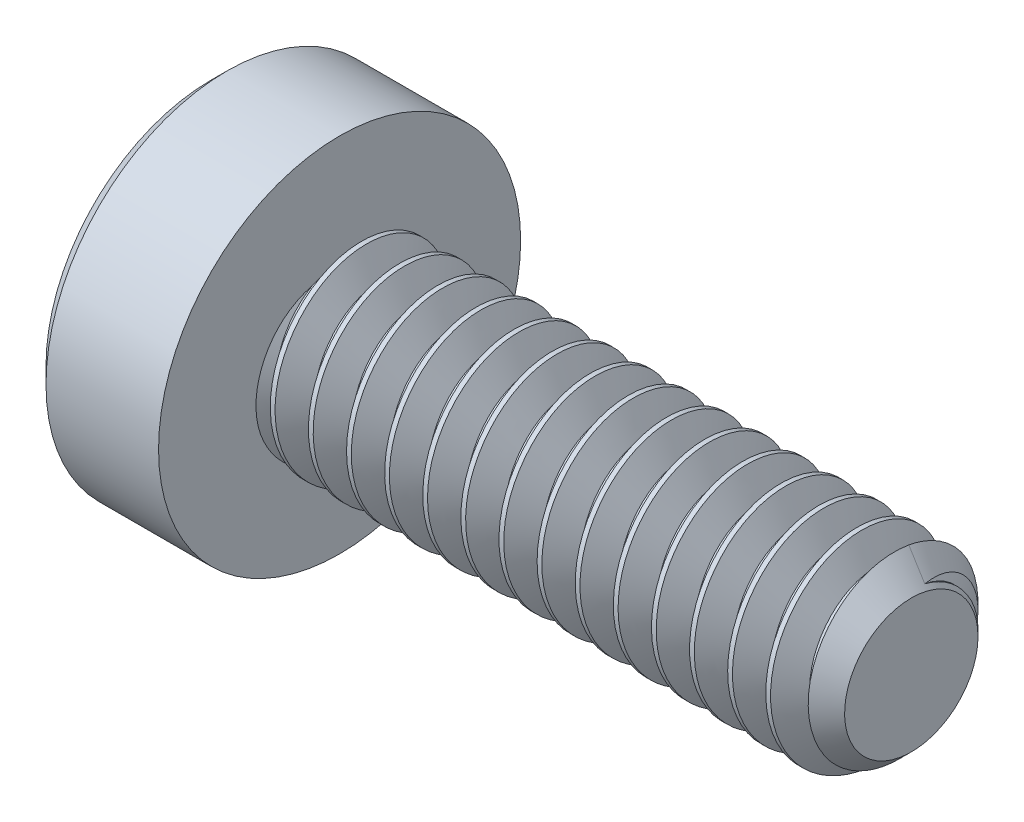
SolidWorks part; units mm, degrees
ref_plane "Front Plane" through (0, 0, 0) normal (0, 0, 1) x (1, 0, 0)
ref_plane "Top Plane" through (0, 0, 0) normal (0, 1, 0) x (1, 0, 0)
ref_plane "Right Plane" through (0, 0, 0) normal (1, 0, 0) x (0, 0, -1)
sketch "Sketch1" plane through (0, 0, 0) normal (0, 0, 1) x (1, 0, 0)
  line L0 (3, 0) -> (-3, 0) construction
  line L1 (3, 1) -> (3, -1) construction
  line L2 (-3, 1.9) -> (-3, -1.9) construction
  line L3 (-3, 1.9) -> (-4.1813, 1.9) construction
  line L4 (-4.1813, 1.9) -> (-4.35, 1.7312) construction
  line L5 (-4.35, 1.7312) -> (-4.35, -1.7313) construction
  line L6 (-4.35, -1.7313) -> (-4.1813, -1.9) construction
  line L7 (-4.1813, -1.9) -> (-3, -1.9) construction
  point P7 (-3.375, 0)
  point P12 (1.4, -1)
  dimension "D1" = 45
  dimension "Dec." = 2
  dimension "Length" = 6
  dimension "Head Dia" = 3.8
  dimension "Head Height" = 1.35
  dimension "Hex Depth" = 0.975
  dimension "Chamfer" = 0.1688
  dimension "D2" = 1.6
ref_plane "Plane1" through (3, 0, 0) normal (1, 0, 0) x (0, 0, -1)
ref_plane "Plane2" through (-4.35, 0, 0) normal (1, 0, 0) x (0, 0, -1)
sketch "Sketch2" plane through (3, 0, 0) normal (1, 0, 0) x (0, 0, -1)
  circle A0 centre (0, 0) radius 1
extrude "Boss-Extrude1" add sketch "Sketch2" against normal up to vertex (6 mm away) up to point (-3, 0, 0)
sketch "Sketch3" plane through (3, 0, 0) normal (1, 0, 0) x (0, 0, -1)
  circle A0 centre (0, 0) radius 1 construction
  circle A1 centre (0, 0) radius 1
curve "Helix/Spiral1" pitch 0.4 height 6.4 radius 1 centre (3, 0, 0) axis (-1, 0, 0) start towards (0, 1, 0) parameters "Pitch"=0.4
chamfer "Chamfer1" distance 0.3 angle 45 1 edges at (3, 0, -1)
sketch "Sketch5" plane through (0, 0, 0) normal (0, 0, 1) x (1, 0, 0)
  line L0 (2.825, 1) -> (3.175, 1)
  line L1 (3.175, 1) -> (3.025, 0.7402)
  line L2 (3.025, 0.7402) -> (2.975, 0.7402)
  line L3 (2.975, 0.7402) -> (2.825, 1)
  line L4 (3, 0.7402) -> (3, 1) construction
  line L5 (2.9, 0.8701) -> (3.1, 0.8701) construction
  dimension "D1" = 60
  dimension "D2" = 0.2
  dimension "D3" = 0.05
sweep "Cut-Sweep1" cut profiles "Sketch5" path "Helix/Spiral1" align with end faces yes
sketch "Sketch4" plane through (-4.35, 0, 0) normal (1, 0, 0) x (0, 0, -1)
  line L0 (-1.9, 0.7937) -> (1.9, 0.7937) construction
  line L1 (0, 0.7506) -> (-0.65, 0.3753)
  line L2 (-0.65, 0.3753) -> (-0.65, -0.3753)
  line L3 (-0.65, -0.3753) -> (0, -0.7506)
  line L4 (0, -0.7506) -> (0.65, -0.3753)
  line L5 (0.65, -0.3753) -> (0.65, 0.3753)
  line L6 (0.65, 0.3753) -> (0, 0.7506)
  line L7 (0, 0) -> (0, 0.7937) construction
  circle A0 centre (0, 0) radius 0.65 construction
  dimension "Hex Size" = 1.3
  dimension "D1" = 3.8
  dimension "D2" = 0.7937
sketch "Sketch6" plane through (0, 0, 0) normal (0, 0, 1) x (1, 0, 0)
  line L0 (-4.1813, 1.9) -> (-4.35, 1.7312) construction
  line L1 (-3, 1.9) -> (-4.1813, 1.9) construction
  line L2 (-3, 1.9) -> (-3, -1.9) construction
  line L3 (-4.35, 1.7312) -> (-4.35, -1.7313) construction
  line L4 (-4.1813, 1.9) -> (-4.35, 1.7312)
  line L5 (-3, 1.9) -> (-4.1813, 1.9)
  line L6 (-3, 1.9) -> (-3, 0)
  line L7 (-4.35, 1.7312) -> (-4.35, 0)
  line L8 (-3, 0) -> (-4.35, 0) construction
  line L9 (-3, 0) -> (-4.35, 0)
revolve "Revolve1" add sketch "Sketch6" angle 360 about L8
extrude "Cut-Extrude1" cut sketch "Sketch4" along normal up to vertex (0.975 mm away) up to point (-3.375, 0, 0)
sketch "Sketch8" plane through (-4.35, 0, 0) normal (-1, 0, 0) x (0, 0, 1)
  circle A1 centre (0, 0) radius 0.7506
extrude "Cut-Extrude2" cut sketch "Sketch8" against normal through all draft 45
equation "\"D3@Helix/Spiral1\" = \"Length@Sketch1\"+\"Pitch@Helix/Spiral1\""
equation "\"D3@Sketch5\" = \"Pitch@Helix/Spiral1\"*.125"
equation "\"D2@Sketch5\" = \"Pitch@Helix/Spiral1\"*.50"
equation "\"D1@Chamfer1\" = \"Pitch@Helix/Spiral1\"*.75"
equation "\"D2@Sketch1\" = \"Pitch@Helix/Spiral1\"*4"
equation "\"D1@Sketch4\" = \"Head Dia@Sketch1\""
equation "\"Chamfer@Sketch1\" = \"Head Height@Sketch1\"/8"
